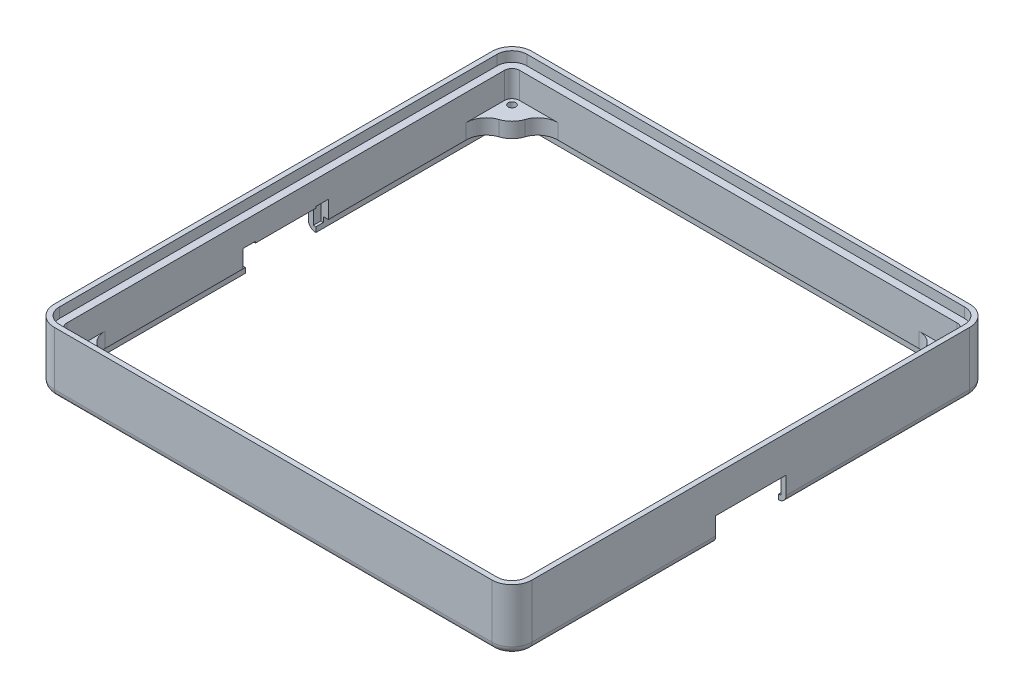
SolidWorks part; units mm, degrees
ref_plane "Front Plane" through (0, 0, 0) normal (0, 0, 1) x (1, 0, 0)
ref_plane "Top Plane" through (0, 0, 0) normal (0, 1, 0) x (1, 0, 0)
ref_plane "Right Plane" through (0, 0, 0) normal (1, 0, 0) x (0, 0, -1)
sketch "Sketch2" plane through (0, 0, 0) normal (0, 1, 0) x (1, 0, 0)
  line L1 (-43.5, -47.5) -> (43.5, -47.5)
  line L2 (-47.5, -43.5) -> (-47.5, 43.5)
  line L3 (-43.5, 47.5) -> (43.5, 47.5)
  line L4 (47.5, -43.5) -> (47.5, 43.5)
  line L5 (-43.5, -43.5) -> (43.5, 43.5) construction
  line L6 (-43.5, 43.5) -> (43.5, -43.5) construction
  arc A0 (-43.5, -47.5) -> (-47.5, -43.5) centre (-43.5, -43.5) cw
  arc A1 (43.5, -47.5) -> (47.5, -43.5) centre (43.5, -43.5) ccw
  arc A2 (43.5, 47.5) -> (47.5, 43.5) centre (43.5, 43.5) cw
  arc A3 (-47.5, 43.5) -> (-43.5, 47.5) centre (-43.5, 43.5) cw
  point P0 (0, 0)
  dimension "D1" = 4
  dimension "D2" = 95
sketch "Sketch3" plane through (0, 0, 0) normal (0, 0, 1) x (1, 0, 0)
  line L0 (0, 0) -> (0, -1.6)
  line L1 (-43.5, 0) -> (43.5, 0) construction
  line L2 (0, -1.6) -> (0, -8.5)
  line L3 (0, -8.5) -> (0, -10)
  dimension "D1" = 1.6
  dimension "D2" = 10
  dimension "D3" = 1.5
extrude "Boss-Extrude1" add sketch "Sketch2" against normal up to vertex (10 mm away) and the other way blind 2.2 up to point (0, -10, 0)
shell "Shell1" thickness 2.5 removed face at (0, -10, 0) removed face at (0, 2.2, 0)
sketch "Sketch4" plane through (0, 0, 0) normal (0, 1, 0) x (1, 0, 0)
  line L19 (-46.5, 43.5) -> (-46.5, -43.5)
  line L20 (-43.5, -46.5) -> (43.5, -46.5)
  line L21 (46.5, -43.5) -> (46.5, 43.5)
  line L22 (43.5, 46.5) -> (-43.5, 46.5)
  line L23 (-46.5, 43.5) -> (-46.5, -43.5)
  line L24 (-43.5, -46.5) -> (43.5, -46.5)
  line L25 (46.5, -43.5) -> (46.5, 43.5)
  line L26 (43.5, 46.5) -> (-43.5, 46.5)
  arc A16 (-46.5, -43.5) -> (-43.5, -46.5) centre (-43.5, -43.5) ccw
  arc A17 (43.5, -46.5) -> (46.5, -43.5) centre (43.5, -43.5) ccw
  arc A18 (46.5, 43.5) -> (43.5, 46.5) centre (43.5, 43.5) ccw
  arc A19 (-43.5, 46.5) -> (-46.5, 43.5) centre (-43.5, 43.5) ccw
  arc A20 (-46.5, -43.5) -> (-43.5, -46.5) centre (-43.5, -43.5) ccw
  arc A21 (43.5, -46.5) -> (46.5, -43.5) centre (43.5, -43.5) ccw
  arc A22 (46.5, 43.5) -> (43.5, 46.5) centre (43.5, 43.5) ccw
  arc A23 (-43.5, 46.5) -> (-46.5, 43.5) centre (-43.5, 43.5) ccw
  dimension "D1" = 1
extrude "Topplate cutout" cut sketch "Sketch4" along normal through all from offset 0.2
fillet "Fillet1" radius 1.5 8 edges at (-46.3284, -10, 46.3284) (-47.5, -10, 0) (-46.3284, -10, -46.3284) (0, -10, -47.5) (46.3284, -10, -46.3284) (47.5, -10, 0) (46.3284, -10, 46.3284) (0, -10, 47.5)
sketch "Sketch5" plane through (0, 0, 0) normal (1, 0, 0) x (0, 0, -1)
  line L0 (-8.5, -4.5) -> (-6, -4.5)
  line L1 (-7, -5) -> (7, -5)
  line L2 (-7, -5) -> (-7, -10)
  line L3 (-7, -10) -> (7, -10)
  line L4 (7, -5) -> (7, -10)
  line L5 (0, -8.5) -> (0, -10) construction
  line L6 (0, -8.5) -> (0, -10) construction
  line L7 (-6, -4.5) -> (-6, -4.8)
  line L8 (-6, -4.8) -> (6, -4.8)
  line L9 (6, -4.8) -> (6, -4.5)
  line L10 (6, -4.5) -> (8.5, -4.5)
  line L11 (-7, -9) -> (-8.5, -9)
  line L13 (-8.5, -9) -> (-8.5, -4.5)
  line L14 (8.5, -4.5) -> (8.5, -9)
  line L15 (8.5, -9) -> (7, -9)
  dimension "D1" = 14
  dimension "D2" = 5
  dimension "D3" = 1
  dimension "D4" = 17
  dimension "D5" = 12
  dimension "D6" = 0.2
  dimension "D7" = 0.5
extrude "connector cutout" cut sketch "Sketch5" against normal through all both and the other way through all contours L4 L1 L2 L3 region at (0, -7.5, 0)
ref_plane "Plane1" through (0, -10, 0) normal (0, 1, 0) x (1, 0, 0)
sketch "Sketch6" plane through (0, -10, 0) normal (0, 1, 0) x (1, 0, 0)
  line L0 (-41, 0) -> (0, 0) construction
  line L1 (-43.5, -43.5) -> (43.5, 43.5) construction
  line L2 (-46, -7) -> (-46, -43.5)
  line L3 (0, 0) -> (0, -32.2074) construction
  line L4 (-46, 7) -> (-41, 7)
  line L5 (-41, 7) -> (-41, -7)
  line L6 (-41, -7) -> (-46, -7)
  line L7 (41, -7) -> (46, -7)
  line L8 (-43.5, -46) -> (43.5, -46)
  line L9 (46, -43.5) -> (46, 43.5)
  line L10 (43.5, 46) -> (-43.5, 46)
  line L11 (-46, 43.5) -> (-46, -43.5)
  line L12 (-43.5, -46) -> (43.5, -46)
  line L13 (46, -43.5) -> (46, -7)
  line L14 (43.5, 46) -> (-43.5, 46)
  line L15 (-46, 43.5) -> (-46, 7)
  line L16 (41, 7) -> (41, -7)
  line L17 (46, 7) -> (41, 7)
  line L18 (46, 7) -> (46, 43.5)
  arc A8 (43.5, -46) -> (46, -43.5) centre (43.5, -43.5) ccw
  arc A9 (46, 43.5) -> (43.5, 46) centre (43.5, 43.5) ccw
  arc A10 (-43.5, 46) -> (-46, 43.5) centre (-43.5, 43.5) ccw
  arc A11 (-46, -43.5) -> (-43.5, -46) centre (-43.5, -43.5) ccw
  arc A12 (43.5, -46) -> (46, -43.5) centre (43.5, -43.5) ccw
  arc A13 (46, 43.5) -> (43.5, 46) centre (43.5, 43.5) ccw
  arc A14 (-43.5, 46) -> (-46, 43.5) centre (-43.5, 43.5) ccw
  arc A15 (-46, -43.5) -> (-43.5, -46) centre (-43.5, -43.5) ccw
  dimension "D2" = 14
  dimension "D3" = 5
  dimension "D1" = 1.5
extrude "Cut-Extrude1" cut sketch "Sketch6" along normal blind 2 contours L2 A15 L12 A12 L13 L7 L16 L17 L18 A13 L14 A14 L15 L4 L5 L6 | L12 A12 L13 L7 L16 L17 L18 A13 L14 A14 L15 L4 L5 L6 L2 A15 region at (0, -10, 0)
extrude "Cut-Extrude2" cut sketch "Sketch5<3>" along normal offset from surface 1 and the other way offset from surface 1 contours L15 L14 L10 L9 L8 L7 L0 L13 L11 L2 L1 L4 region at (0, -4.6759, 7.25) up to face at (47.5, -4.95, 0) other way up to face at (-47.5, -4.95, 0)
sketch "Sketch5<3>" plane through (0, 0, 0) normal (1, 0, 0) x (0, 0, -1) same geometry as "Sketch5"
sketch "Sketch8" plane through (0, -8, 0) normal (0, -1, 0) x (1, 0, 0)
  circle A0 centre (-43.5, 43.5) radius 4
  circle A1 centre (43.5, 43.5) radius 4
  circle A2 centre (43.5, -43.5) radius 4
  circle A3 centre (-43.5, -43.5) radius 4
  circle A4 centre (-43.5, 43.5) radius 0.75
  circle A5 centre (43.5, 43.5) radius 0.75
  circle A6 centre (-43.5, -43.5) radius 0.75
  circle A7 centre (43.5, -43.5) radius 0.75
  dimension "D1" = 1.5
extrude "Boss-Extrude3" add sketch "Sketch8" against normal blind 3
fillet "Fillet2" radius 4 8 edges at (-45, -6.5, -39.7919) (-39.7919, -6.5, -45) (45, -6.5, -39.7919) (39.7919, -6.5, -45) (45, -6.5, 39.7919) (39.7919, -6.5, 45) (-39.7919, -6.5, 45) (-45, -6.5, 39.7919)
